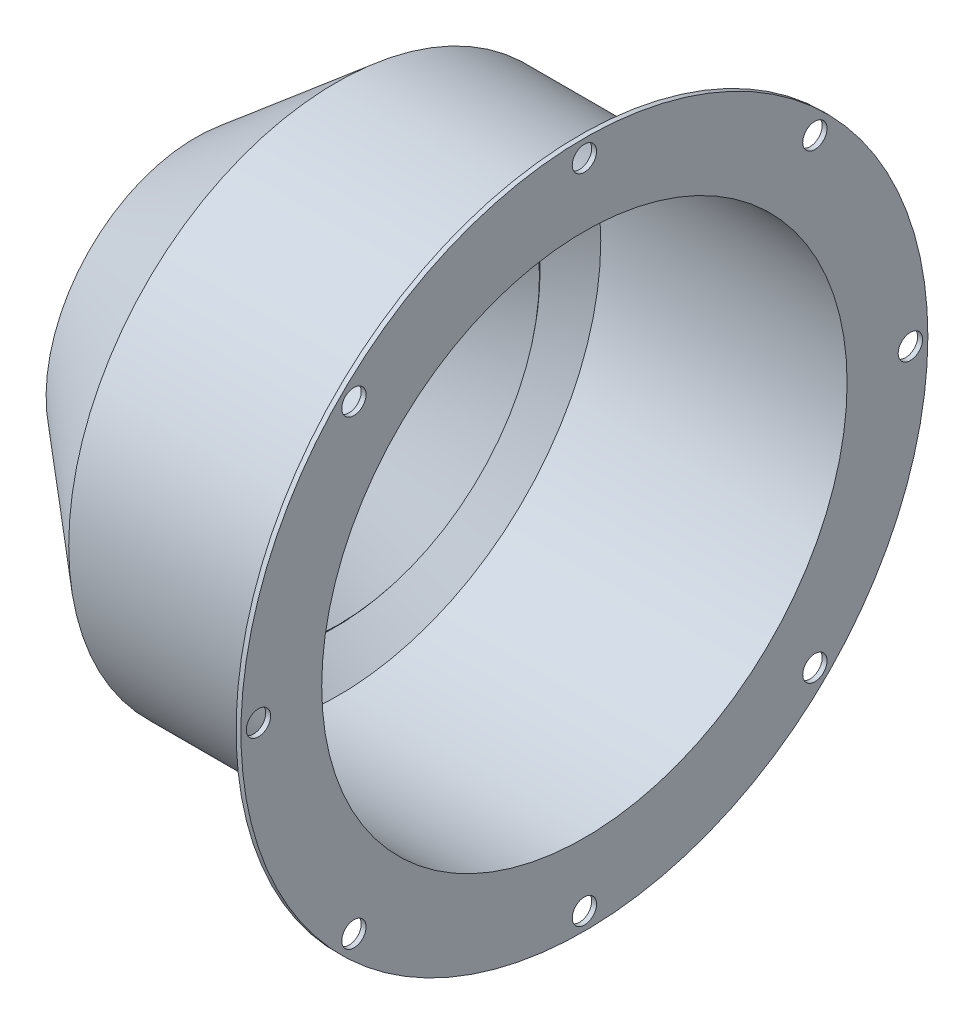
SolidWorks part; units mm, degrees
ref_plane "Front Plane" through (0, 0, 0) normal (0, 0, 1) x (1, 0, 0)
ref_plane "Top Plane" through (0, 0, 0) normal (0, 1, 0) x (1, 0, 0)
ref_plane "Right Plane" through (0, 0, 0) normal (1, 0, 0) x (0, 0, -1)
sketch "Sketch2" plane through (-67.3276, 12.9644, 6.3798) normal (0, 0, -1) x (1, 0, 0)
  line L0 (19.05, 89.662) -> (19.05, 68.58)
  line L1 (19.05, 89.7128) -> (19.05, -89.7128) construction
  line L2 (19.05, 89.662) -> (17.78, 89.662)
  line L3 (17.78, 89.662) -> (17.78, 69.85)
  line L4 (19.05, 76.2) -> (19.05, -76.2) construction
  line L5 (19.05, 68.58) -> (-45.2578, 68.58)
  line L6 (-45.2578, 68.58) -> (-81.5824, 38.1)
  line L7 (-81.5824, 38.1) -> (-82.3987, 39.0729)
  line L8 (-82.3987, 39.0729) -> (-45.72, 69.85)
  line L9 (-45.72, 69.85) -> (17.78, 69.85)
  line L10 (41.3304, 0) -> (-77.7743, 0) construction
  line L11 (87.376, 0) -> (4.7958, 0) construction
  point P4 (-52.5031, 69.85)
  dimension "D1" = 21.082
  dimension "D2" = 1.27
  dimension "D3" = 1.27
  dimension "D4" = 89.662
  dimension "D5" = 1.27
  dimension "D6" = 40
  dimension "D7" = 38.1
  dimension "D8" = 63.5
revolve "Revolve1" add sketch "Sketch2" angle 360 about L10
sketch "Sketch4" plane through (88.3744, 12.9644, 6.3798) normal (0, 0, 1) x (1, 0, 0)
  line L0 (-200.9598, 52.578) -> (-263.2659, 0.2969)
  line L2 (-263.2659, 0.2969) -> (-264.0822, 1.2698)
  line L3 (-264.0822, 1.2698) -> (-201.7761, 53.5509)
  line L4 (-201.7761, 53.5509) -> (-200.9598, 52.578)
  line L5 (-166.2127, 0) -> (-290.4908, 0) construction
  point P4 (-265.4555, 0)
  point P11 (-270.0796, 0.3801)
  point P12 (-263.2659, 0.2969)
  dimension "D1" = 1.27
  dimension "D2" = 40
  dimension "D3" = 52.578
revolve "Revolve4" add sketch "Sketch4" angle 360 about L5
sketch "Sketch5" plane through (-49.5476, 0, 0) normal (-1, 0, 0) x (0, 0, 1)
  circle A0 centre (6.3798, 98.0544) radius 3.175
  circle A1 centre (66.5475, 73.1322) radius 3.175
  circle A2 centre (91.4698, 12.9644) radius 3.175
  circle A3 centre (66.5475, -47.2033) radius 3.175
  circle A4 centre (6.3798, -72.1256) radius 3.175
  circle A5 centre (-53.7879, -47.2033) radius 3.175
  circle A6 centre (-78.7102, 12.9644) radius 3.175
  circle A7 centre (-53.7879, 73.1322) radius 3.175
  point P20 (6.3798, 12.9644)
  dimension "D1" = 6.35
  dimension "D2" = 85.09
  dimension "D3" = 8
extrude "Cut-Extrude1" cut sketch "Sketch5" against normal blind 2.54
sketch "Sketch6" plane through (88.3744, 12.9644, 6.3798) normal (0, 0, 1) x (1, 0, 0)
  line L0 (-240.9299, 35.2196) -> (-233.0808, 25.8653)
  line L1 (-233.0808, 25.8653) -> (-223.352, 34.0287)
  line L2 (-223.352, 34.0287) -> (-231.2012, 43.383)
  line L3 (-231.2012, 43.383) -> (-240.9299, 35.2196)
  line L4 (-160.8493, 0) -> (-248.4528, 0) construction
  line L5 (-68.326, 0) -> (-150.9062, 0) construction
  point P8 (-229.5588, 44.5716)
  point P9 (-229.6391, 44.5558)
  point P10 (-235.0498, 24.2131)
  point P11 (-231.2012, 43.383)
  dimension "D1" = 12.7
  dimension "D2" = 40
extrude "Boss-Extrude1" add sketch "Sketch6" along normal mid plane 1.27
pattern_circular "CirPattern1" count 4 over 360 about axis through (-113.0476, 12.9644, 6.3798) along (-1, 0, 0) of "Boss-Extrude1"
